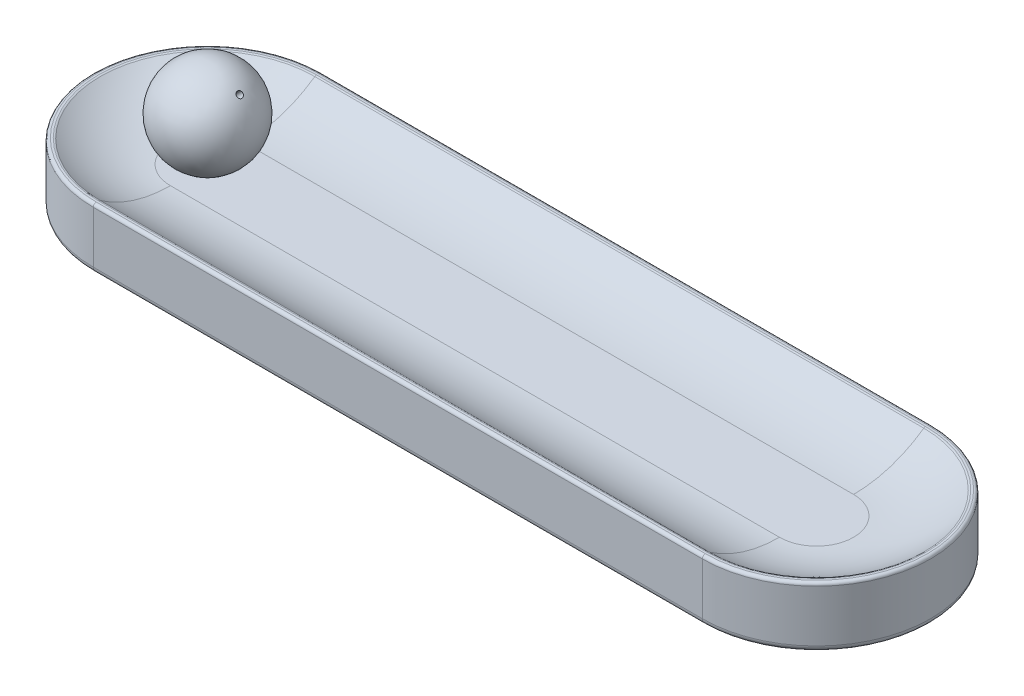
SolidWorks part; units mm, degrees
ref_plane "Front Plane" through (0, 0, 0) normal (0, 0, 1) x (1, 0, 0)
ref_plane "Top Plane" through (0, 0, 0) normal (0, 1, 0) x (1, 0, 0)
ref_plane "Right Plane" through (0, 0, 0) normal (1, 0, 0) x (0, 0, -1)
sketch "Sketch1" plane through (0, 0, 0) normal (0, 1, 0) x (1, 0, 0)
  line L0 (-100, 0) -> (100, 0) construction
  line L1 (-100, 37.5) -> (100, 37.5)
  line L2 (-100, -37.5) -> (100, -37.5)
  arc A0 (-100, 37.5) -> (-100, -37.5) centre (-100, 0) ccw
  arc A1 (100, -37.5) -> (100, 37.5) centre (100, 0) ccw
  point P3 (0, 0)
  dimension "D1" = 200
  dimension "D2" = 75
extrude "Boss-Extrude1" add sketch "Sketch1" along normal blind 20
sketch "Sketch2" plane through (0, 20, 0) normal (0, 1, 0) x (1, 0, 0)
  line L4 (-100, -35.5) -> (100, -35.5)
  line L5 (100, 35.5) -> (-100, 35.5)
  line L6 (-100, -35.5) -> (100, -35.5)
  line L7 (100, 35.5) -> (-100, 35.5)
  arc A4 (-100, 35.5) -> (-100, -35.5) centre (-100, 0) ccw
  arc A5 (100, -35.5) -> (100, 35.5) centre (100, 0) ccw
  arc A6 (-100, 35.5) -> (-100, -35.5) centre (-100, 0) ccw
  arc A7 (100, -35.5) -> (100, 35.5) centre (100, 0) ccw
  dimension "D1" = 2
extrude "Cut-Extrude1" cut sketch "Sketch2" against normal blind 7.5
fillet "Fillet1" radius 40 2 edges at (0, 12.5, -35.5) (0, 12.5, 35.5)
fillet "Fillet2" radius 1 8 edges at (0, 20, -35.5) (135.5, 20, 0) (0, 20, 35.5) (0, 20, -37.5) (137.5, 20, 0) (0, 20, 37.5) (-135.5, 20, 0) (-137.5, 20, 0)
fillet "Fillet3" radius 2 4 edges at (0, 0, 37.5) (137.5, 0, 0) (0, 0, -37.5) (-137.5, 0, 0)
sketch "Sketch4" plane through (0, 0, 0) normal (0, 0, 1) x (1, 0, 0)
  line L0 (-100, 12) -> (-100, 42) construction
  line L1 (-100, 19) -> (-100, 2) construction
  line L2 (100, 12.5) -> (-100, 12.5) construction
  line L3 (-100, 12) -> (-100, 42)
  arc A0 (-100, 42) -> (-100, 12) centre (-100, 27) ccw
  point P4 (-150, 11.2673)
  dimension "D3" = 15
  dimension "D1" = 30
  dimension "D2" = 0.5
revolve "Revolve1" add sketch "Sketch4" angle 360 about L0
sketch "Sketch5" plane through (0, 0, 0) normal (0, 0, 1) x (1, 0, 0)
  line L0 (-100, 27) -> (90.9188, 217.9188) construction
  line L1 (-100, 27) -> (-100, 42) construction
  line L2 (-100, 20) -> (100, 20) construction
  arc A0 (-96.1594, 12.5) -> (-103.8406, 12.5) centre (-100, 27) ccw construction
  point P8 (0, 0)
  dimension "D1" = 15
  dimension "D2" = 45
  dimension "D3" = 270
ref_plane "Plane1" through (-25.8934, -25.8934, 0) normal (0.7071, 0.7071, 0) x (0.7071, -0.7071, 0)
sketch "Sketch6" plane through (-25.8934, -25.8934, 0) normal (0.7071, 0.7071, 0) x (0.7071, -0.7071, 0)
  line L0 (-89.8026, 0) -> (-100.4092, 0) construction
  circle A0 centre (-89.8026, 0) radius 1
  point P4 (-124.1018, 0)
  dimension "D1" = 2
extrude "Cut-Extrude2" cut sketch "Sketch6" against normal up to vertex (15 mm away) up to point (-100, 27, 0)
